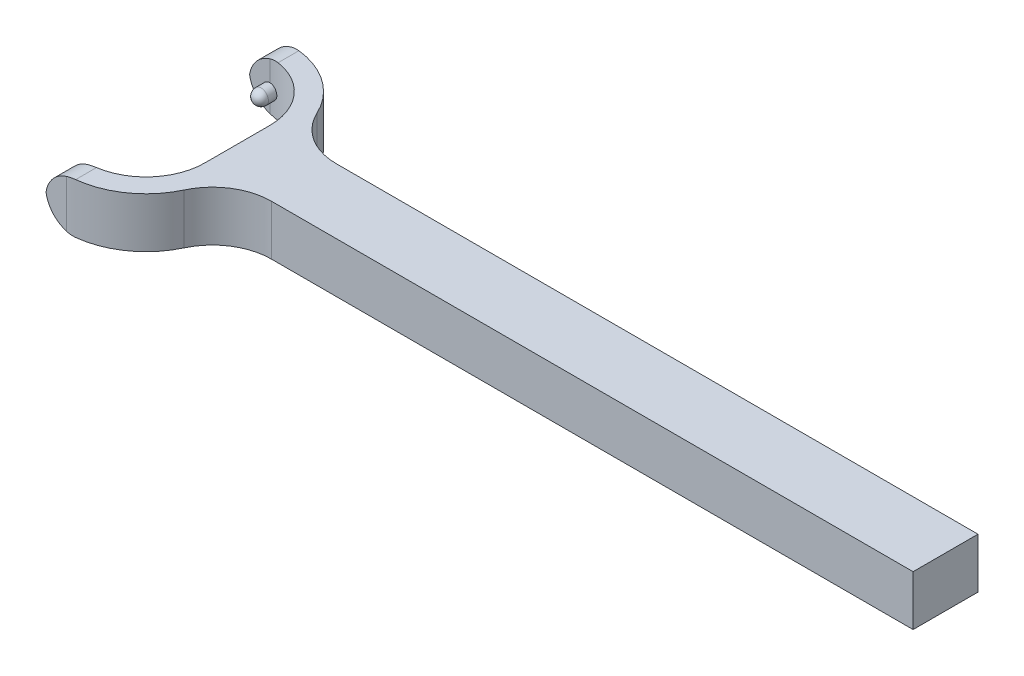
SolidWorks part; units mm, degrees
ref_plane "Front Plane" through (0, 0, 0) normal (0, 0, 1) x (1, 0, 0)
ref_plane "Top Plane" through (0, 0, 0) normal (0, 1, 0) x (1, 0, 0)
ref_plane "Right Plane" through (0, 0, 0) normal (1, 0, 0) x (0, 0, -1)
sketch "Sketch1" plane through (0, 0, 0) normal (1, 0, 0) x (0, 0, -1)
  line L1 (0, 0) -> (11, 0)
  line L2 (0, 0) -> (0, -8.5)
  line L3 (0, -8.5) -> (11, -8.5)
  line L4 (11, 0) -> (11, -8.5)
  dimension "D1" = 11
  dimension "D2" = 8.5
extrude "Boss-Extrude1" add sketch "Sketch1" along normal blind 120
ref_plane "Plane2" through (0, -4.25, 0) normal (0, 1, 0) x (1, 0, 0)
sketch "Sketch17" plane through (0, 0, 0) normal (0, 1, 0) x (1, 0, 0)
  line L0 (-10, -10) -> (-13.5, -10)
  line L1 (-13.5, -10) -> (-13.5, -13.5)
  line L2 (-13.5, -13.5) -> (-10, -13.5)
  line L4 (-23.4629, 5.5) -> (20.4079, 5.5) construction
  line L5 (120, 0) -> (0, 0) construction
  line L20 (3.5, 0) -> (3.5, 11)
  line L22 (-13.5, 24.5) -> (-10, 24.5)
  line L23 (0, 0) -> (0, 11)
  line L24 (-13.5, 21) -> (-13.5, 24.5)
  line L25 (-10, 21) -> (-13.5, 21)
  arc A0 (-10, -10) -> (0, 0) centre (-10, 0) ccw
  arc A2 (-10, -13.5) -> (3.5, 0) centre (-10, 0) ccw
  arc A3 (-10, 24.5) -> (3.5, 11) centre (-10, 11) cw
  arc A4 (-10, 21) -> (0, 11) centre (-10, 11) cw
  dimension "D3" = 20
  dimension "D6" = 3.5
  dimension "D1" = 0
  dimension "D2" = 10
  dimension "D5" = 3.5
  dimension "D7" = 5.5
extrude "Boss-Extrude3" add sketch "Sketch17" along normal blind 8.5 from offset 8.5 offset against normal yes
fillet "Fillet5" radius 10 2 edges at (3.5, -4.25, 0) (3.5, -4.25, -11)
fillet "Fillet6" radius 5 4 edges at (-13.5, 0, 11.75) (-13.5, -8.5, 11.75) (-13.5, -8.5, -22.75) (-13.5, 0, -22.75)
sketch "Sketch18" plane through (0, 0, -21) normal (0, 0, 1) x (1, 0, 0)
  line L2 (-10, -0.2303) -> (-10, -8.2697) construction
  line L3 (0, 0) -> (-8.5, 0) construction
  circle A0 centre (-10, -5) radius 1.25
  dimension "D1" = 2.5
  dimension "D2" = 0
  dimension "D3" = 5
extrude "Boss-Extrude4" add sketch "Sketch18" along normal blind 1.5
sketch "Sketch19" plane through (0, 0, 10) normal (0, 0, -1) x (-1, 0, 0)
  line L0 (10, -0.2303) -> (10, -8.2697) construction
  circle A0 centre (10, -3.5) radius 1.25
  dimension "D1" = 2.5
  dimension "D2" = 5
extrude "Boss-Extrude5" add sketch "Sketch19" along normal blind 1.5
ref_plane "CenterOfClips" through (-7.5, 0, 0) normal (-1, 0, 0) x (0, 0, 1)
sketch "Sketch24" plane through (0, 0, 8.5) normal (0, 0, -1) x (-1, 0, 0)
  line L0 (10, -2.25) -> (10, -4.75)
  circle A0 centre (10, -3.5) radius 1.25 construction
  arc A1 (10, -4.75) -> (10, -2.25) centre (10, -3.5) ccw
revolve "Revolve9" add sketch "Sketch24" angle 180 about L0
sketch "Sketch25" plane through (0, 0, -19.5) normal (0, 0, 1) x (1, 0, 0)
  line L0 (-10, -3.75) -> (-10, -6.25)
  circle A0 centre (-10, -5) radius 1.25 construction
  arc A1 (-10, -3.75) -> (-10, -6.25) centre (-10, -5) ccw
revolve "Revolve10" add sketch "Sketch25" angle 180 about L0 reverse direction yes
